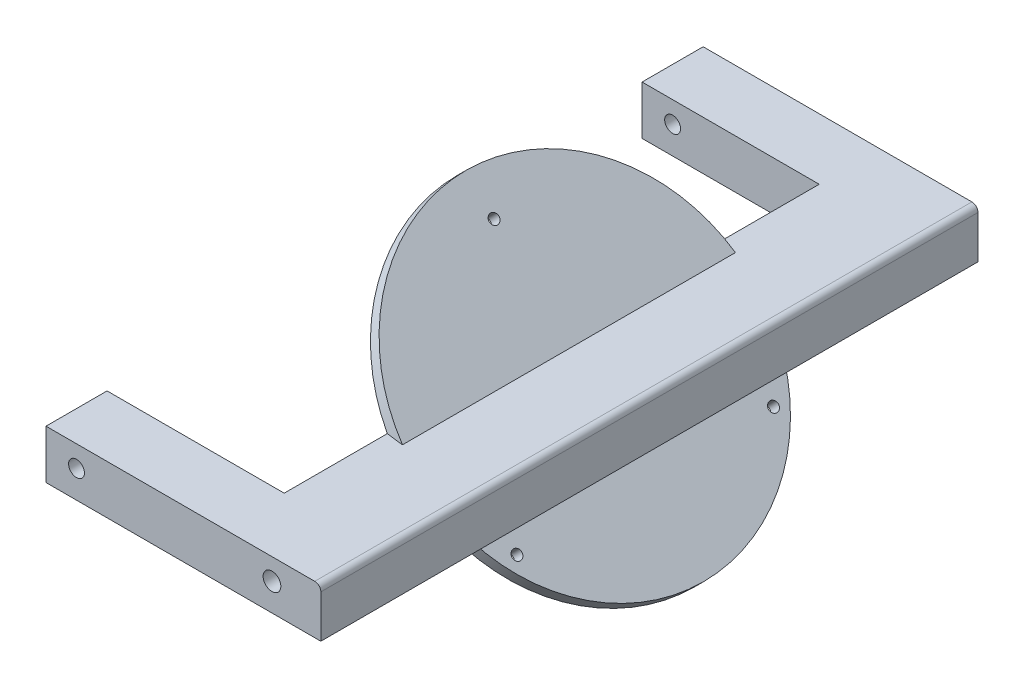
SolidWorks part; units mm, degrees
material "Nylon 101"
ref_plane "Front Plane" through (0, 0, 0) normal (0, 0, 1) x (1, 0, 0)
ref_plane "Top Plane" through (0, 0, 0) normal (0, 1, 0) x (1, 0, 0)
ref_plane "Right Plane" through (0, 0, 0) normal (1, 0, 0) x (0, 0, -1)
sketch "Sketch1" plane through (0, 0, 0) normal (0, 0, 1) x (1, 0, 0)
  line L4 (8, 4) -> (-8, 4)
  line L6 (0, -4) -> (-8, 4)
  line L7 (0, 4) -> (0, -4) construction
  line L8 (8, 4) -> (8, -4)
  line L9 (8, -4) -> (0, -4)
  dimension "D1" = 8
  dimension "D2" = 45
extrude "Base" add sketch "Sketch1" along normal mid plane 107.6
sketch "Sketch4" plane through (-2, -2, 0) normal (-0.7071, -0.7071, 0) x (0, 0, 1)
  line L0 (-53.8, 2.8284) -> (53.8, 2.8284) construction
  line L1 (-53.8, 8.4853) -> (-53.8, -2.8284) construction
  line L2 (53.8, 8.4853) -> (53.8, -2.8284) construction
  line L3 (0, 8.4853) -> (0, -2.8284) construction
  line L4 (53.8, 8.4853) -> (-53.8, 8.4853) construction
  line L6 (53.8, -2.8284) -> (-53.8, -2.8284) construction
  line L7 (-17.5, 20.3284) -> (17.5, 20.3284)
  line L8 (-17.5, 20.3284) -> (-17.5, -14.6716)
  line L9 (-17.5, -14.6716) -> (17.5, -14.6716)
  line L10 (17.5, 20.3284) -> (17.5, -14.6716)
  line L11 (-17.5, 20.3284) -> (17.5, -14.6716) construction
  line L12 (-17.5, -14.6716) -> (17.5, 20.3284) construction
  circle A0 centre (0, 2.8284) radius 27.5
  point P16 (0, 2.8284)
  point P17 (0, 2.8284)
  line M5 (53.8, 8.4853) -> (-53.8, 8.4853)
  dimension "D1" = 55
  dimension "D2" = 35
extrude "Boss-Extrude2" add sketch "Sketch4" against normal blind 2 contours A0 L8 L7 L10 M5 | L10 L7 L8 M5 | A0 L10 L9 L8 | A0 L8 M5 | L10 L8 L9 | L10 L8 M5 | A0 L10 M5 region at (-16.475, 12.475, 0) region at (-12.1872, 8.1872, 0) region at (0.1872, -4.1872, 0) region at (0.1872, -4.1872, -18.1422)
hole_wizard "M2x0.4 Tapped Hole1" positions "Sketch5" profile "Sketch6" tap size "M2x0.4" standard "ANSI Metric" end condition through all
sketch "Sketch5" plane through (-0.5858, -0.5858, 0) normal (0.7071, 0.7071, 0) x (0.7071, -0.7071, 0)
  line L4 (-8.4853, 0) -> (2.8284, 0) construction
  line L5 (-20.3284, 17.5) -> (-20.3284, -17.5) construction
  line L6 (-20.3284, -17.5) -> (14.6716, -17.5) construction
  line L7 (14.6716, 17.5) -> (14.6716, -17.5) construction
  line L8 (-20.3284, 17.5) -> (14.6716, 17.5) construction
  point P0 (-23.8284, 0)
  point P2 (11.1716, 21)
  point P4 (11.1716, -21)
  dimension "D1" = 3.5
  dimension "D2" = 3.5
  dimension "D3" = 3.5
  dimension "D4" = 3.5
sketch "Sketch6" plane through (-17.435, 16.2635, 0) normal (0, 0, 1) x (-0.7071, 0.7071, 0)
  line L0 (0, 0) -> (0, 29.5)
  line L1 (0, 29.5) -> (0.8, 29.5)
  line L2 (0.8, 29.5) -> (0.8, 0)
  line L5 (0.8, 0) -> (0, 0)
  line L11 (0, -6.35) -> (0, 107.95) construction
  dimension "Thru Tap Drill Dia." = 1.6
  dimension "Thru Tap Drill Depth" = 29.5
cosmetic thread "Hole Thread1" parameters "D2"=2
cosmetic thread "Hole Thread2" parameters "D2"=2
cosmetic thread "Hole Thread3" parameters "D2"=2
ref_plane "Plane1" through (-2, 2, 0) normal (0.7071, -0.7071, 0) x (0, 0, 1)
sketch "Sketch8" plane through (-2, 2, 0) normal (0.7071, -0.7071, 0) x (0, 0, 1)
  line L0 (0, 3.8284) -> (0, 2.8284)
  line L1 (27.5, 2.8284) -> (-27.5, 2.8284) construction
  line L2 (0, 2.8284) -> (-12, 2.8284)
  line L4 (0, 2.8284) -> (0, 10.3284) construction
  line L5 (-6.5, 10.3284) -> (-12, 2.8284)
  arc A1 (-6.5, 10.3284) -> (0, 3.8284) centre (0, 10.3284) ccw
  dimension "D2" = 6.5
  dimension "D1" = 1
  dimension "D3" = 12
revolve "Revolve1" add sketch "Sketch8" angle 360 about L4
fillet "Fillet1" radius 0.5 1 edges at (-13.8995, -0.7071, 0)
hole_wizard "Side Holes" positions "Sketch2" profile "Sketch3" hole size "M2.5" standard "ANSI Metric" end condition through all
sketch "Sketch2" plane through (0, 0, 53.8) normal (0, 0, 1) x (1, 0, 0)
  line L0 (0, 0.5) -> (0, 4) construction
  line L1 (8, 4) -> (-8, 4) construction
  line L3 (-4.5, 0.5) -> (8, 0.5) construction
  line L4 (-8, 4) -> (0, -4) construction
  line L6 (8, -4) -> (8, 4) construction
  point P0 (0, 0.5)
  dimension "D1" = 3.5
sketch "Sketch3" plane through (0, 0.5, 53.8) normal (1, 0, 0) x (0, -1, 0)
  line L0 (0, 0) -> (0, 107.6)
  line L1 (0, 107.6) -> (1.45, 107.6)
  line L2 (1.45, 107.6) -> (1.45, 0)
  line L5 (1.45, 0) -> (0, 0)
  line L11 (0, -6.35) -> (0, 107.95) construction
  dimension "Thru Hole Dia." = 2.9
  dimension "Thru Hole Depth" = 107.6
sketch "Sketch9" plane through (0, 0, 53.8) normal (0, 0, 1) x (1, 0, 0)
  line L0 (-8, 4) -> (0, -4)
  line L1 (0, -4) -> (-37, -4)
  line L2 (-37, -4) -> (-37, 4)
  line L3 (-37, 4) -> (-8, 4)
  line L4 (8, -4) -> (8, 4) construction
  dimension "D1" = 45
extrude "Side Arm" add sketch "Sketch9" against normal blind 10
mirror "Mirror1" about plane through (0, 0, 0) normal (0, 0, 1) of "Side Arm"
hole_wizard "M2 Clearance Hole1" positions "Sketch10" profile "Sketch11" hole size "M2" standard "ANSI Metric" end condition through all
sketch "Sketch10" plane through (0, 0, 53.8) normal (0, 0, 1) x (1, 0, 0)
  line L0 (-37, 4) -> (-37, -4) construction
  point P0 (-32, 0.5)
  dimension "D1" = 5
sketch "Sketch11" plane through (-32, 0.5, 53.8) normal (1, 0, 0) x (0, -1, 0)
  line L0 (0, 0) -> (0, 107.6)
  line L1 (0, 107.6) -> (1.3, 107.6)
  line L2 (1.3, 107.6) -> (1.3, 0)
  line L5 (1.3, 0) -> (0, 0)
  line L11 (0, -6.35) -> (0, 107.95) construction
  dimension "Thru Hole Dia." = 2.6
  dimension "Thru Hole Depth" = 107.6
fillet "Fillet2" radius 1 1 edges at (8, 4, 0)
